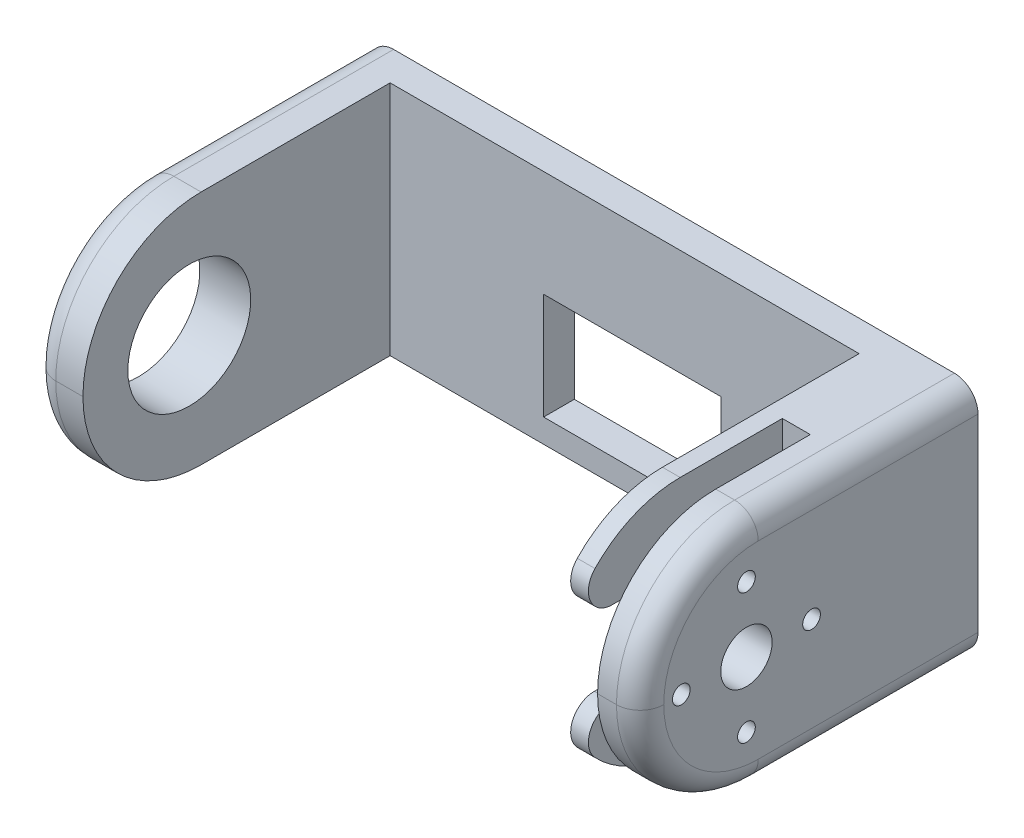
SolidWorks part; units mm, degrees
material "PET"
ref_plane "Front Plane" through (0, 0, 0) normal (0, 0, 1) x (1, 0, 0)
ref_plane "Top Plane" through (0, 0, 0) normal (0, 1, 0) x (1, 0, 0)
ref_plane "Right Plane" through (0, 0, 0) normal (1, 0, 0) x (0, 0, -1)
sketch "Sketch1" plane through (0, 0, 0) normal (0, 0, 1) x (1, 0, 0)
  line L0 (0, 0) -> (10.9985, 6.35) construction
  line L1 (10.9985, 6.35) -> (4.9661, 16.7986) construction
  line L2 (4.9661, 16.7986) -> (-1.8382, 12.8701) construction
  line L3 (-2.4732, 12.7) -> (-63.5, 12.7) construction
  line L4 (-63.5, 22.86) -> (-63.5, 2.54) construction
  line L5 (-60.96, 0) -> (-0.6806, 0) construction
  line L6 (-60.96, 25.4) -> (-0.6806, 25.4) construction
  line L8 (1.8594, 22.86) -> (1.8594, 2.54) construction
  line L10 (-63.5, 0) -> (1.8594, 0)
  line L11 (-63.5, 0) -> (-63.5, 25.4)
  line L12 (-63.5, 25.4) -> (1.8594, 25.4)
  line L13 (1.8594, 0) -> (1.8594, 25.4)
  arc A0 (-63.5, 2.54) -> (-60.96, 0) centre (-60.96, 2.54) ccw construction
  arc A1 (-1.8382, 12.8701) -> (-2.4732, 12.7) centre (-2.4732, 13.97) cw construction
  arc A2 (-63.5, 22.86) -> (-60.96, 25.4) centre (-60.96, 22.86) cw construction
  arc A3 (1.8594, 22.86) -> (-0.6806, 25.4) centre (-0.6806, 22.86) ccw construction
  arc A4 (1.8594, 2.54) -> (-0.6806, 0) centre (-0.6806, 2.54) cw construction
  point P9 (-63.5, 0)
  point P16 (-63.5, 25.4)
  dimension "D6" = 2.54
  dimension "D7" = 1.27
  dimension "D8" = 2.54
  dimension "D1" = 12.065
  dimension "D2" = 12.7
  dimension "D3" = 68.5886
  dimension "D4" = 63.5
  dimension "D5" = 12.7
extrude "Boss-Extrude1" add sketch "Sketch1" along normal blind 36.322
sketch "Sketch4" plane through (0, 25.4, 0) normal (0, 1, 0) x (1, 0, 0)
  line L0 (-58.0338, -36.322) -> (-58.0338, -3.302)
  line L1 (1.8594, -36.322) -> (-63.5, -36.322) construction
  line L2 (-58.0338, -3.302) -> (-7.6148, -3.302)
  line L3 (-7.6148, -3.302) -> (-7.6148, -36.322)
  line L4 (-7.6148, -36.322) -> (-58.0338, -36.322)
  line L5 (-5.7098, -36.322) -> (-5.7098, -13.462)
  line L6 (-5.7098, -13.462) -> (-2.7126, -13.462)
  line L7 (-2.7126, -13.462) -> (-2.7126, -36.322)
  line L8 (-5.7098, -36.322) -> (-2.7126, -36.322)
  line L9 (1.8594, -36.322) -> (1.8594, 0) construction
  line L10 (1.8594, 0) -> (-63.5, 0) construction
  dimension "D1" = 2.9972
  dimension "D2" = 4.572
  dimension "D3" = 22.86
  dimension "D4" = 50.419
  dimension "D5" = 1.905
  dimension "D6" = 3.302
extrude "Cut-Extrude1" cut sketch "Sketch4" against normal through all
sketch "Sketch5" plane through (1.8594, 0, 0) normal (1, 0, 0) x (0, 0, -1)
  line L0 (-36.322, 0) -> (-36.322, 25.4) construction
  circle A0 centre (-24.892, 12.7) radius 2.7622
  point P6 (-36.322, 12.7)
  dimension "D1" = 5.5245
  dimension "D2" = 11.43
extrude "Cut-Extrude2" cut sketch "Sketch5" against normal up to next
sketch "Sketch6" plane through (1.8594, 0, 0) normal (1, 0, 0) x (0, 0, -1)
  circle A0 centre (-24.892, 12.7) radius 0.9525
  circle A1 centre (-24.892, 19.7) radius 0.9525
  circle A2 centre (-17.892, 12.7) radius 0.9525
  circle A3 centre (-24.892, 5.7) radius 0.9525
  circle A4 centre (-31.892, 12.7) radius 0.9525
  point P14 (-24.892, 12.7)
  dimension "D1" = 1.905
  dimension "D2" = 7
  dimension "D3" = 4
extrude "Cut-Extrude3" cut sketch "Sketch6" against normal up to surface (9.4742 mm away) up to face at (-7.6148, 12.7, 19.812)
sketch "Sketch7" plane through (-63.5, 0, 0) normal (-1, 0, 0) x (0, 0, 1)
  circle A0 centre (24.892, 12.7) radius 0.9525 construction
  circle A1 centre (24.892, 12.7) radius 0.9525 construction
  circle A2 centre (24.892, 12.7) radius 6.604
  dimension "D1" = 13.208
extrude "Cut-Extrude5" cut sketch "Sketch7" against normal up to next contours A2 A1 | A1 region at (-63.5, 12.7, 24.892)
sketch "Sketch8" plane through (-7.6148, 0, 0) normal (-1, 0, 0) x (0, 0, 1)
  line L0 (36.322, 25.4) -> (36.322, 0) construction
  line L1 (36.322, 17.2) -> (23.622, 17.2)
  line L2 (36.322, 17.2) -> (36.322, 8.2)
  line L3 (36.322, 8.2) -> (23.622, 8.2)
  arc A0 (23.622, 17.2) -> (23.622, 8.2) centre (23.622, 12.7) ccw
  point P6 (36.322, 12.7)
  dimension "D1" = 4.5
  dimension "D2" = 12.7
extrude "Cut-Extrude6" cut sketch "Sketch8" against normal up to next
fillet "Fillet1" radius 12.7 6 edges at (-60.7669, 0, 36.322) (-6.6623, 0, 36.322) (-0.4266, 0, 36.322) (-0.4266, 25.4, 36.322) (-6.6623, 25.4, 36.322) (-60.7669, 25.4, 36.322)
fillet "Fillet2" radius 2.54 10 edges at (1.8594, 0, 11.811) (1.8594, 3.7197, 32.6023) (1.8594, 21.6803, 32.6023) (-63.5, 0, 11.811) (-63.5, 3.7197, 32.6023) (-63.5, 21.6803, 32.6023) (1.8594, 25.4, 11.811) (-6.6623, 8.2, 36.322) (-6.6623, 17.2, 36.322) (-63.5, 25.4, 11.811)
sketch "Sketch9" plane through (0, 0, 3.302) normal (0, 0, 1) x (1, 0, 0)
  line L0 (-63.5, 12.7) -> (1.8594, 12.7) construction
  line L2 (-39.0753, 6.985) -> (-22.5653, 6.985)
  line L3 (-39.0753, 6.985) -> (-39.0753, 18.415)
  line L4 (-39.0753, 18.415) -> (-22.5653, 18.415)
  line L5 (-22.5653, 6.985) -> (-22.5653, 18.415)
  line L6 (-39.0753, 6.985) -> (-22.5653, 18.415) construction
  line L7 (-39.0753, 18.415) -> (-22.5653, 6.985) construction
  point P4 (-30.8203, 12.7)
  dimension "D1" = 16.51
  dimension "D2" = 11.43
sketch "Sketch10" plane through (0, 0, 0) normal (0, 0, -1) x (-1, 0, 0)
  line L1 (22.4823, 13.97) -> (41.5323, 13.97)
  line L2 (22.4823, 13.97) -> (22.4823, 2.54)
  line L3 (22.4823, 2.54) -> (41.5323, 2.54)
  line L4 (41.5323, 13.97) -> (41.5323, 2.54)
extrude "Cut-Extrude7" cut sketch "Sketch10" against normal through all
